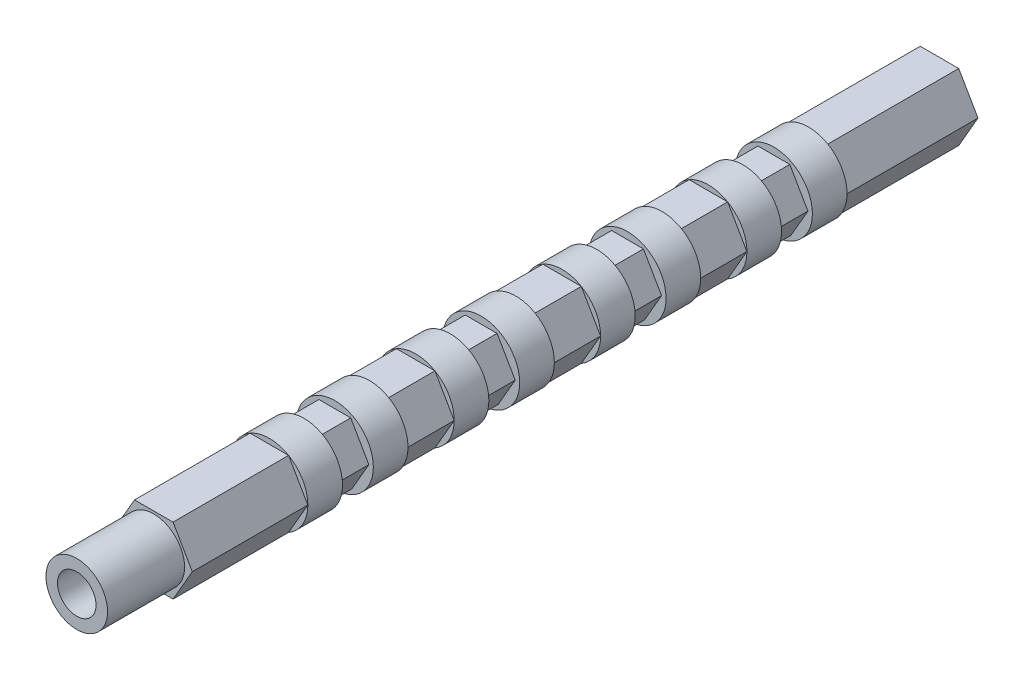
SolidWorks part; units mm, degrees
ref_plane "Front Plane" through (0, 0, 0) normal (0, 0, 1) x (1, 0, 0)
ref_plane "Top Plane" through (0, 0, 0) normal (0, 1, 0) x (1, 0, 0)
ref_plane "Right Plane" through (0, 0, 0) normal (1, 0, 0) x (0, 0, -1)
other "Configuration Table"
sketch "Sketch1" plane through (0, 0, 0) normal (0, 0, 1) x (1, 0, 0)
  line L1 (2.5, -4.3301) -> (5, 0)
  line L2 (5, 0) -> (2.5, 4.3301)
  line L3 (2.5, 4.3301) -> (-2.5, 4.3301)
  line L4 (-2.5, 4.3301) -> (-5, 0)
  line L5 (-5, 0) -> (-2.5, -4.3301)
  line L6 (-2.5, -4.3301) -> (2.5, -4.3301)
  circle A0 centre (0, 0) radius 4.3301 construction
  circle A1 centre (0, 0) radius 5 construction
  dimension "D1" = 10
extrude "Boss-Extrude1" add sketch "Sketch1" along normal blind 51 and the other way blind 51
sketch "Sketch2" plane through (0, 0, 51) normal (0, 0, 1) x (1, 0, 0)
  circle A0 centre (0, 0) radius 4
  dimension "D1" = 8
extrude "Boss-Extrude2" add sketch "Sketch2" along normal blind 10
sketch "Sketch3" plane through (0, 0, 61) normal (0, 0, 1) x (1, 0, 0)
  circle A0 centre (0, 0) radius 2.5
  dimension "D1" = 5
extrude "Cut-Extrude1" cut sketch "Sketch3" against normal blind 8
sketch "Sketch4" plane through (0, 0, 53) normal (0, 0, 1) x (1, 0, 0)
  circle A0 centre (0, 0) radius 1.75
  dimension "D1" = 3.5
extrude "Cut-Extrude2" cut sketch "Sketch4" against normal blind 30
sketch "Sketch5" plane through (0, 0, -51) normal (0, 0, -1) x (-1, 0, 0)
  circle A0 centre (0, 0) radius 1.7
  dimension "D1" = 3.4
extrude "Cut-Extrude3" cut sketch "Sketch5" against normal blind 30
sketch "Sketch6" plane through (0, 4.3301, 0) normal (0, 1, 0) x (1, 0, 0)
  line L0 (-2.5, -29.5) -> (2.5, -29.5)
  line L1 (-2.5, 51) -> (-2.5, -51) construction
  line L2 (2.5, 51) -> (2.5, -51) construction
  line L3 (2.5, -51) -> (-2.5, -51) construction
  point P6 (0, 0)
  dimension "D1" = 21.5
ref_plane "Plane1" through (0, 0, 29.5) normal (0, 0, 1) x (1, 0, 0)
sketch "Sketch7" plane through (0, 0, 29.5) normal (0, 0, 1) x (1, 0, 0)
  circle A0 centre (0, 0) radius 5
extrude "Boss-Extrude3" add sketch "Sketch7" along normal blind 6.5 and the other way blind 6.5
sketch "Sketch8" plane through (0, 0, 29.5) normal (0, 0, 1) x (1, 0, 0)
  line L32 (-2.067, 4.0801) -> (2.067, 4.0801)
  line L37 (4.4226, 0) -> (2.067, 4.0801)
  line L38 (-2.067, 4.0801) -> (-4.4226, 0)
  line L39 (-4.4226, 0) -> (-2.2113, -3.8301)
  line L40 (-2.2113, -3.8301) -> (2.2113, -3.8301)
  line L41 (2.2113, -3.8301) -> (4.4226, 0)
  line L42 (4.4226, 0) -> (2.067, 4.0801)
  line L43 (-2.067, 4.0801) -> (-4.4226, 0)
  line L44 (-4.4226, 0) -> (-2.2113, -3.8301)
  line L45 (-2.2113, -3.8301) -> (2.2113, -3.8301)
  line L46 (2.2113, -3.8301) -> (4.4226, 0)
  dimension "D1" = 0.5
extrude "Cut-Extrude-Thin2" cut sketch "Sketch8" against normal blind 2 and the other way blind 2 thin thin type one direction wall 2
pattern_linear "LPattern1" count 4 spacing 19 along (0, 0, -1) of "Boss-Extrude3", "Cut-Extrude-Thin2"
